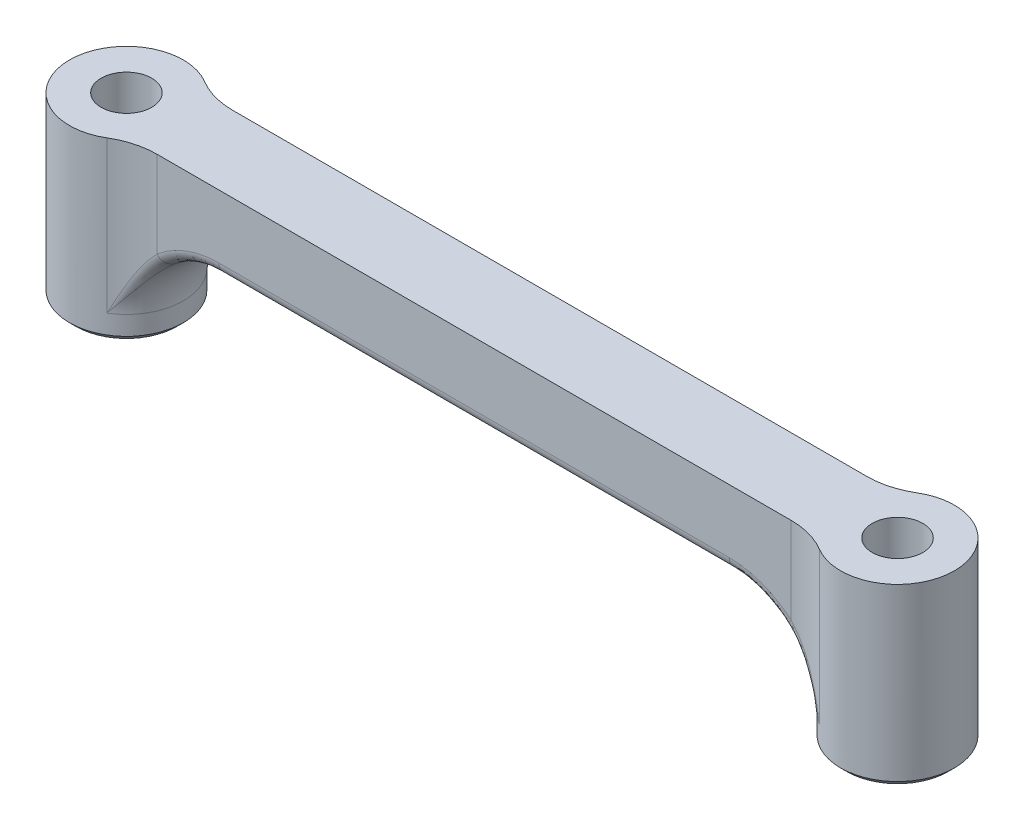
SolidWorks part; units mm, degrees
ref_plane "Front Plane" through (0, 0, 0) normal (0, 0, 1) x (1, 0, 0)
ref_plane "Top Plane" through (0, 0, 0) normal (0, 1, 0) x (1, 0, 0)
ref_plane "Right Plane" through (0, 0, 0) normal (1, 0, 0) x (0, 0, -1)
sketch "Sketch1" plane through (0, 0, 0) normal (0, 1, 0) x (1, 0, 0)
  line L1 (-13.5629, 1.5) -> (0, 1.5)
  line L2 (-13.5629, 1.5) -> (-13.5629, -1.5)
  line L3 (-13.5629, -1.5) -> (0, -1.5)
  line L4 (0, 1.5) -> (0, -1.5)
  circle A0 centre (-15.24, 0) radius 1
  circle A1 centre (-15.24, 0) radius 2.25
  point P8 (0, 0)
  point P9 (0, 0)
  point P10 (-14.6495, 1.2799)
  dimension "D2" = 2
  dimension "D3" = 4.5
  dimension "D1" = 15.24
  dimension "D4" = 3
extrude "Boss-Extrude1" add sketch "Sketch1" along normal blind 3 contours A1 L3 L4 L1 | L2 A1 A0 | L2 A1 region at (-13.3311, 0, 0) region at (-6.5861, 0, 0) region at (-13.6227, 0, 0)
extrude "Boss-Extrude2" add sketch "Sketch1<3>" against normal blind 4 contours L2 A1 | L2 A1 A0 region at (-13.3311, 0, 0) region at (-13.6227, 0, 0)
sketch "Sketch1<3>" plane through (0, 0, 0) normal (0, 1, 0) x (1, 0, 0) same geometry as "Sketch1"
fillet "Fillet1" radius 3 3 edges at (-12.99, 0, 0) (-13.5629, 1.5, -1.5) (-13.5629, 1.5, 1.5)
mirror "Mirror1" about plane through (0, 3, 0) normal (1, 0, 0) of bodies 103
fillet "Fillet2" radius 0.5 10 edges at (-13.4876, -2.0323, -1.655) (-11.5213, -0.2684, -1.5) (13.4876, -2.0323, -1.655) (11.5213, -0.2684, -1.5) (-13.4876, -2.0323, 1.655) (-11.5156, -0.266, 1.5) (13.4876, -2.0323, 1.655) (11.5156, -0.266, 1.5) (0, 0, -1.5) (0, 0, 1.5)
chamfer "Chamfer1" distance 0.25 angle 45 2 edges at (-15.24, -4, 2.25) (15.24, -4, 2.25)
